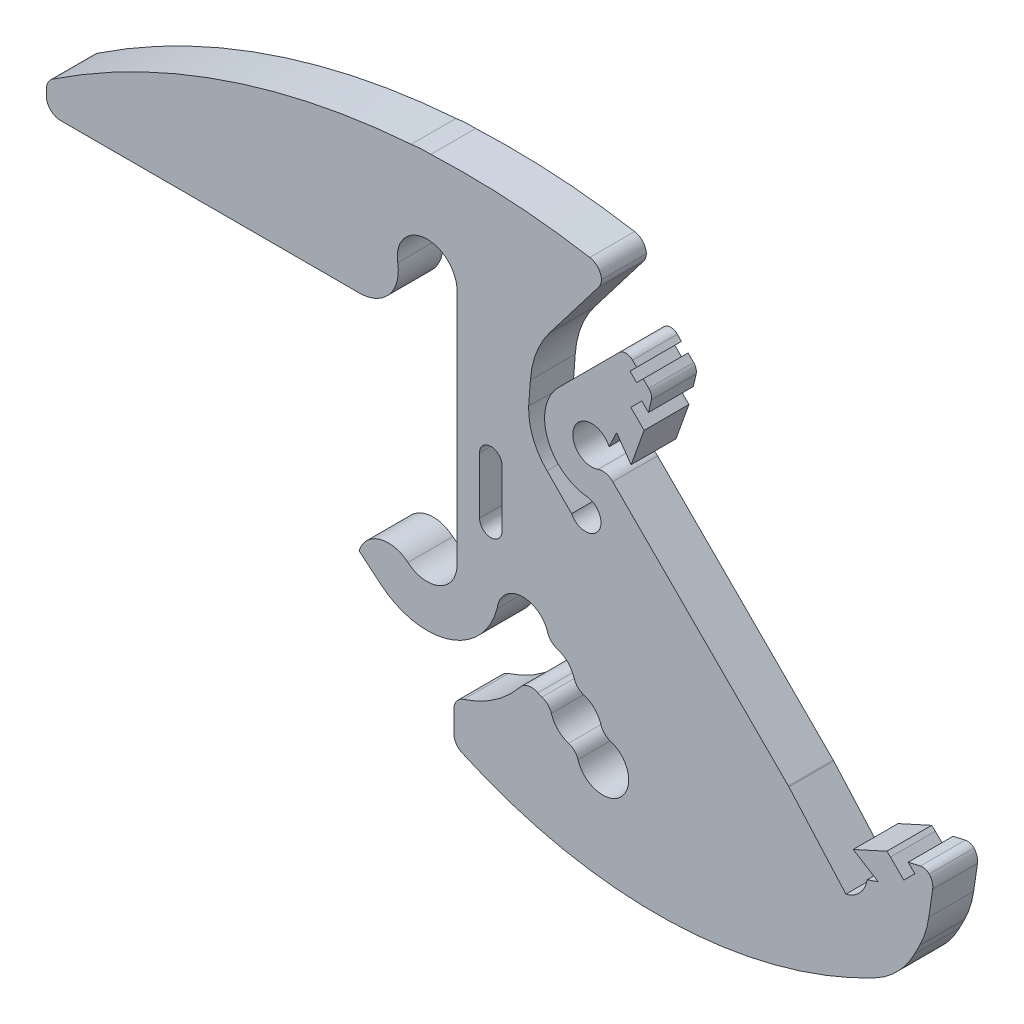
SolidWorks part; units mm, degrees
ref_plane "Front Plane" through (0, 0, 0) normal (0, 0, 1) x (1, 0, 0)
ref_plane "Top Plane" through (0, 0, 0) normal (0, 1, 0) x (1, 0, 0)
ref_plane "Right Plane" through (0, 0, 0) normal (1, 0, 0) x (0, 0, -1)
sketch "Main Geometry" plane through (0, 0, 0) normal (0, 0, 1) x (1, 0, 0)
  line L0 (0, -26.7735) -> (0, 29.7025) construction
  line L1 (-29.8398, 0) -> (33.7757, 0) construction
  line L2 (18, -21.6476) -> (18, 5) construction
  line L3 (18, 5) -> (48.2234, -25.2234) construction
  dimension "vertical offset" = 5
  dimension "horizontal offset" = 18
  dimension "device angle" = 45
sketch "Cart Clip Geometry" plane through (0, 0, 0) normal (0, 0, 1) x (1, 0, 0)
  line L0 (18, 9.2735) -> (18, -10.0482) construction
  line L1 (11.175, 4.575) -> (7.675, -8.575)
  line L2 (7.0852, 12.575) -> (-7.0852, 12.575) construction
  line L3 (-29.8398, 0) -> (33.7757, 0) construction
  line L4 (18, -21.6476) -> (18, 5) construction
  line L6 (-7.0852, 0) -> (7.0852, 0) construction
  line L7 (7.0852, -12.575) -> (-7.0852, -12.575) construction
  line L8 (0, 12.575) -> (-7.5717, 11.2399) construction
  line L9 (0, -12.575) -> (-5.2448, -18.8255) construction
  line L10 (3.175, 12.575) -> (3.175, -12.575)
  line L11 (-11.0052, 10.6345) -> (-10.7668, 9.2824)
  line L12 (-4.9334, -18.4544) -> (-7.2315, -16.526)
  line L13 (11.175, 4.575) -> (11.175, 12.575)
  line L14 (7.675, -12.575) -> (7.675, -8.575)
  arc A0 (-3.1268, 12.0237) -> (3.175, 12.575) centre (0, 12.575) cw
  arc A1 (-2.0409, -15.0072) -> (3.175, -12.575) centre (0, -12.575) ccw
  arc A2 (-11.0052, 10.6345) -> (11.175, 12.575) centre (0, 12.575) cw
  arc A3 (-4.9334, -18.4544) -> (7.675, -12.575) centre (0, -12.575) ccw
  arc A4 (-3.1268, 12.0237) -> (-10.7668, 9.2824) centre (-7.182, 11.3086) cw
  arc A5 (-2.0409, -15.0072) -> (-7.2315, -16.526) centre (-4.1299, -17.4968) ccw
  point P5 (0, 12.575)
  point P10 (0, 0)
  point P36 (18, -0.3874)
  dimension "D1" = 4
  dimension "rail radius" = 3.175
  dimension "bottom rail radius" = 3.175
  dimension "rail separation" = 12.575
  dimension "top clip grab angle" = 10
  dimension "bottom clip grab angle" = 50
  dimension "top clip thickness" = 8
  dimension "bottom clip thickness" = 4.5
  dimension "top clip end extension" = 1.3729
  dimension "bottom clip end extension" = 3
  dimension "top clip vertical extension" = 8
extrude "Cart Clip" add sketch "Cart Clip Geometry" against normal blind 4.7625
sketch "Device Clip Geometry" plane through (0, 0, 0) normal (0, 0, 1) x (1, 0, 0)
  line L0 (35.1404, -4.3761) -> (36.0403, -3.4762) construction
  line L1 (22.2452, 15.0879) -> (21.5381, 14.3808)
  line L2 (44.5165, -21.5165) -> (18, 5)
  line L3 (18, 5) -> (48.2234, -25.2234) construction
  line L4 (18, 5) -> (20.2451, 7.2451)
  line L5 (21.6593, 5.8309) -> (20.2451, 7.2451)
  line L6 (21.6593, 5.8309) -> (23.0381, 9.6846)
  line L7 (23.0381, 9.6846) -> (21.6239, 11.0988)
  line L8 (21.6239, 11.0988) -> (22.7977, 12.2726)
  line L9 (22.7977, 12.2726) -> (23.5048, 11.5655)
  line L10 (23.5048, 11.5655) -> (23.8045, 12.8639)
  line L11 (23.5372, 13.7959) -> (22.9502, 14.3828)
  line L12 (20.3936, 15.5253) -> (13.9341, 9.0659)
  line L13 (13.9341, 1.9948) -> (41.5113, -25.5824)
  line L14 (53.3124, -15.9793) -> (53.8993, -16.5663)
  line L15 (51.082, -16.0117) -> (52.3804, -15.712)
  line L16 (51.7891, -16.7188) -> (51.082, -16.0117)
  line L17 (50.6153, -17.8926) -> (51.7891, -16.7188)
  line L18 (49.2011, -16.4784) -> (50.6153, -17.8926)
  line L19 (45.3474, -17.8572) -> (49.2011, -16.4784)
  line L20 (45.3474, -17.8572) -> (46.7616, -19.2714)
  line L21 (44.5165, -21.5165) -> (46.7616, -19.2714)
  line L22 (55.0418, -19.1229) -> (48.5824, -25.5824)
  line L23 (21.5381, 14.3808) -> (22.2431, 13.6757)
  line L25 (22.2431, 13.6757) -> (22.9502, 14.3828)
  line L26 (22.2452, 15.0879) -> (21.8078, 15.5253)
  line L27 (53.1922, -17.2734) -> (53.8993, -16.5663)
  line L28 (53.8973, -17.9784) -> (53.1922, -17.2734)
  line L29 (54.6044, -17.2713) -> (53.8973, -17.9784)
  line L30 (54.6044, -17.2713) -> (55.0418, -17.7087)
  arc A0 (23.8045, 12.8639) -> (23.5372, 13.7959) centre (22.8301, 13.0888) ccw
  arc A1 (21.8078, 15.5253) -> (20.3936, 15.5253) centre (21.1007, 14.8182) ccw
  arc A2 (53.3124, -15.9793) -> (52.3804, -15.712) centre (52.6053, -16.6864) ccw
  arc A3 (55.0418, -17.7087) -> (55.0418, -19.1229) centre (54.3347, -18.4158) cw
  arc A4 (48.5824, -25.5824) -> (41.5113, -25.5824) centre (45.0468, -22.0468) cw
  arc A5 (13.9341, 9.0659) -> (13.9341, 1.9948) centre (17.4697, 5.5303) ccw
  point P3 (35.5903, -3.9262)
  point P17 (31.2583, -8.2583)
  point P28 (27.7227, -11.7938)
  point P30 (23.9291, 13.404)
  point P33 (21.1007, 16.2324)
  point P36 (52.9205, -15.5874)
  point P39 (55.7489, -18.4158)
  point P42 (45.0468, -29.1179)
  point P45 (10.3986, 5.5303)
  dimension "D2" = 1
  dimension "D3" = 1
  dimension "D5" = 5
  dimension "D1" = 4
  dimension "plate thickness" = 3.175
  dimension "board mating width" = 20.5
  dimension "board catch step" = 1
  dimension "plate to board offset" = 3.7
  dimension "board thickness" = 1.66
  dimension "above board offset" = 1.6
  dimension "overall width" = 24.5
  dimension "base thickness" = 5
  dimension "plate width" = 18.75
  dimension "D4" = 16.75
  dimension "board holding step" = 18.5
  dimension "D6" = 1.6186
  dimension "D7" = 0.9971
extrude "Device Clip" add sketch "Device Clip Geometry" against normal blind 4.7625
sketch "Device Clip Flex Relief Geometry" plane through (0, 0, 0) normal (0, 0, 1) x (1, 0, 0)
  line L0 (35.5903, -3.9262) -> (36.0403, -3.4762) construction
  circle A0 centre (17.4697, 5.5303) radius 2
  dimension "D1" = 4
sketch "Joint Geometry" plane through (0, 0, 0) normal (0, 0, 1) x (1, 0, 0)
  line L0 (7.675, -8.575) -> (41.5113, -25.5824)
  line L1 (41.5113, -25.5824) -> (13.9341, 1.9948)
  line L2 (13.9341, 1.9948) -> (11.175, 4.575)
  line L3 (11.175, 4.575) -> (7.675, -8.575)
extrude "Joint" add sketch "Joint Geometry" against normal blind 4.7625
fillet "joint fillets" radius 1 4 edges at (7.675, -8.575, -2.3813) (41.5113, -25.5824, -2.3813) (13.9341, 1.9948, -2.3813) (11.175, 4.575, -2.3813)
extrude "Device Clip Flex Relief" cut sketch "Device Clip Flex Relief Geometry" against normal through all
sketch "mark2" plane through (0, 0, 0) normal (0, 0, 1) x (1, 0, 0)
  circle A1 centre (3.175, 3.3755) radius 0.75
sketch "mark3" plane through (0, 0, 0) normal (0, 0, 1) x (1, 0, 0)
  circle A2 centre (3.175, 1.3755) radius 0.75
sketch "mark4" plane through (0, 0, 0) normal (0, 0, 1) x (1, 0, 0)
  circle A3 centre (3.175, -0.6245) radius 0.75
sketch "mark5" plane through (0, 0, 0) normal (0, 0, 1) x (1, 0, 0)
  circle A4 centre (3.175, -2.6245) radius 0.75
sketch "mark6" plane through (0, 0, 0) normal (0, 0, 1) x (1, 0, 0)
  circle A5 centre (3.175, -4.6245) radius 0.75
sketch "mark7" plane through (0, 0, 0) normal (0, 0, 1) x (1, 0, 0)
  circle A6 centre (3.175, -6.6245) radius 0.75
sketch "mark8" plane through (0, 0, 0) normal (0, 0, 1) x (1, 0, 0)
  circle A7 centre (3.175, -8.6245) radius 0.75
extrude "marker1" [suppressed] cut sketch "mark2" against normal blind 25
extrude "marker2" [suppressed] cut sketch "mark3" against normal blind 25
extrude "marker3" [suppressed] cut sketch "mark4" against normal blind 25
extrude "marker4" [suppressed] cut sketch "mark5" against normal blind 25
extrude "marker5" [suppressed] cut sketch "mark6" against normal blind 25
extrude "marker6" [suppressed] cut sketch "mark7" against normal blind 25
extrude "marker7" [suppressed] cut sketch "mark8" against normal blind 25
sketch "Sketch5" plane through (0, 0, 0) normal (0, 0, 1) x (1, 0, 0)
  line L0 (44.4701, -22.2536) -> (38.3891, -15.3891)
  line L1 (44.5165, -21.5165) -> (18.8839, 4.1161) construction
  line L2 (46.7616, -19.2714) -> (38.3891, -15.3891)
  line L3 (46.7616, -19.2714) -> (44.5165, -21.5165) construction
  arc A0 (46.7616, -19.2714) -> (44.4701, -22.2536) centre (43.7623, -19.3383) cw
extrude "SNAP IN RELIEF" cut sketch "Sketch5" against normal blind 6.35
sketch "BOTTOM BEEFUP SKETCH" plane through (0, 0, 0) normal (0, 0, 1) x (1, 0, 0)
  line L0 (10.677, -13.8895) -> (7.5264, -14.0782)
  line L1 (10.675, -9.2825) -> (44.2787, -25.4887)
  line L2 (44.2787, -25.4887) -> (53.8993, -16.5663)
  line L3 (53.8993, -16.5663) -> (55.0418, -17.7087)
  line L4 (50.3984, -26.8103) -> (55.3333, -21.8754)
  line L5 (7.5264, -14.0782) -> (7.2086, -8.7723)
  line L6 (7.2086, -8.7723) -> (10.675, -9.2825)
  line L7 (11.894, -16.9554) -> (10.677, -13.8895)
  line L8 (2.8283, -24.9304) -> (2.8283, -29.2389)
  arc A0 (55.0418, -17.7087) -> (55.3333, -21.8754) centre (52.7908, -19.9597) cw
  arc A1 (11.894, -16.9554) -> (2.8283, -24.9304) centre (0, -12.575) cw
  arc A2 (50.3984, -26.8103) -> (2.8283, -29.2389) centre (24.3794, 15.7331) cw
  arc A3 (-4.9334, -18.4544) -> (7.675, -12.575) centre (0, -12.575) ccw construction
  dimension "D1" = 5
extrude "BOTTOM BEEFUP" add sketch "BOTTOM BEEFUP SKETCH" against normal blind 4.7625
sketch "CABLE HOLE" plane through (0, 0, 0) normal (0, 0, 1) x (1, 0, 0)
  circle A0 centre (10.1626, -14.8178) radius 2.75
  dimension "D1" = 5.5
extrude "CABLE HOLE CUT" cut sketch "CABLE HOLE" against normal blind 6.35
sketch "BOX SLIDE BEEF" plane through (0, 0, 0) normal (0, 0, 1) x (1, 0, 0)
  line L0 (-7.182, 7.1908) -> (-40.4406, 7.1908)
  line L1 (-40.4406, 7.1908) -> (-40.4406, 10.131)
  line L2 (-40.4406, 10.131) -> (-4.1553, 22.9487)
  line L3 (-4.1553, 22.9487) -> (-7.182, 7.1908)
  arc A0 (-10.7668, 9.2824) -> (-3.1268, 12.0237) centre (-7.182, 11.3086) ccw construction
  arc A1 (11.175, 12.575) -> (-11.0052, 10.6345) centre (0, 12.575) ccw construction
extrude "SHELF TAIL" add sketch "BOX SLIDE BEEF" against normal blind 4.7625
sketch "BEHIND TOP CLIP BEEF SKETCH" plane through (0, 0, 0) normal (0, 0, 1) x (1, 0, 0)
  line L0 (18.5184, 20.8412) -> (11.175, 11.2548)
  line L1 (18.5184, 20.8412) -> (18.5184, 22.4809)
  line L2 (18.5184, 22.4809) -> (0.5901, 23.7344)
  line L3 (0.5901, 23.7344) -> (11.175, 11.2548)
  line L4 (11.175, 5.009) -> (11.175, 12.575) construction
  arc A0 (11.175, 12.575) -> (-4.1553, 22.9487) centre (0, 12.575) ccw construction
extrude "FRONT TAB BEEF" add sketch "BEHIND TOP CLIP BEEF SKETCH" against normal blind 4.7625
sketch "TOP CURVE" plane through (0, 0, 0) normal (0, 0, 1) x (1, 0, 0)
  line L0 (-40.4406, 10.131) -> (-38.7511, 8.7519)
  line L1 (-38.7511, 8.7519) -> (0, 16.8685)
  line L2 (0, 16.8685) -> (13.1756, 16.8685)
  line L3 (13.1756, 16.8685) -> (18.5184, 22.4809)
  arc A0 (-40.4406, 10.131) -> (18.5184, 22.4809) centre (4.0052, -55.1441) cw
extrude "TOP CURVE EXTRUSION" add sketch "TOP CURVE" against normal blind 4.7625
pattern_linear "LPattern1" count 4 spacing 4 along (0.7071, -0.7071, 0) of "CABLE HOLE CUT"
sketch "Sketch13" plane through (0, 0, 0) normal (0, 0, 1) x (1, 0, 0)
  line L0 (49.2011, -16.4784) -> (48.8113, -16.1381)
  line L1 (45.3474, -17.8572) -> (45.2375, -17.7613)
  line L2 (45.2375, -17.7613) -> (48.8113, -16.1381)
  line L3 (45.3474, -17.8572) -> (49.2011, -16.4784)
extrude "POSCON BOTTOM SNAPBEEF" add sketch "Sketch13" against normal blind 4.7625
sketch "Sketch14" plane through (0, 0, 0) normal (0, 0, 1) x (1, 0, 0)
  line L3 (12.7141, 0.8179) -> (15.3366, -1.8287)
  line L5 (12.471, 5.6443) -> (11.175, 11.2548)
  line L6 (11.175, 11.2548) -> (10.7789, 5.768)
  arc A0 (13.9181, 2.0109) -> (16.9732, 0.555) centre (17.4697, 5.5303) ccw
  arc A1 (12.471, 5.6443) -> (13.9181, 2.0109) centre (17.4697, 5.5303) ccw
  arc A2 (16.9732, 0.555) -> (15.3366, -1.8287) centre (16.8094, -1.0861) cw
  arc A3 (10.7789, 5.768) -> (12.7141, 0.8179) centre (17.4697, 5.5303) ccw
extrude "POSCON TOP CLIP FLEX RELIEF" cut sketch "Sketch14" against normal blind 6.35
sketch "Sketch15" plane through (0, 0, 0) normal (0, 0, 1) x (1, 0, 0)
  line L0 (6.7591, -1.122) -> (6.7591, -7.122) construction
  line L1 (7.9591, -1.122) -> (7.9591, -7.122)
  line L2 (5.5591, -1.122) -> (5.5591, -7.122)
  arc A0 (7.9591, -1.122) -> (5.5591, -1.122) centre (6.7591, -1.122) ccw
  arc A1 (5.5591, -7.122) -> (7.9591, -7.122) centre (6.7591, -7.122) ccw
  point P2 (6.7591, -4.122)
  dimension "D2" = 1.2
  dimension "D1" = 6
extrude "ZIP TIE SLOT" cut sketch "Sketch15" against normal blind 6.35
sketch "Sketch16" plane through (0, 0, 0) normal (0, 0, 1) x (1, 0, 0)
  line L0 (45.2375, -17.7613) -> (47.9015, -19.3975)
  line L1 (47.9015, -19.3975) -> (45.9622, -20.0708)
  line L2 (45.9622, -20.0708) -> (45.2375, -17.7613)
  line L3 (53.7888, -16.4558) -> (53.0401, -21.5945)
  line L4 (53.0401, -21.5945) -> (50.3984, -26.8103)
  line L5 (50.3984, -26.8103) -> (52.008, -28.2076)
  line L6 (52.008, -28.2076) -> (59.8175, -20.2354)
  line L7 (53.7888, -16.4558) -> (59.8175, -20.2354)
  line L8 (55.0418, -17.7087) -> (53.3124, -15.9793) construction
extrude "POSCON BOTTOM SNAP RELIEF" cut sketch "Sketch16" against normal blind 6.35
fillet "SMALL FILLET" radius 1.5 15 edges at (18.5184, 20.8412, -2.3813) (-40.4406, 7.1908, -2.3813) (12.9115, -14.8974, -2.3813) (15.7399, -17.7258, -2.3813) (18.5683, -20.5542, -2.3813) (13.0706, -20.3951, -2.3813) (15.899, -23.2235, -2.3813) (38.3891, -15.3891, -2.3813) (18.8839, 4.1161, -2.3813) (18.5184, 22.4809, -2.3813) (-40.4406, 10.131, -2.3813) (53.7888, -16.4558, -2.3813) (2.8283, -29.2389, -2.3813) (2.8283, -24.9304, -2.3813) (10.7667, -19.2633, -2.3813)
sketch "Sketch12" plane through (0, 0, 0) normal (0, 0, 1) x (1, 0, 0)
  line L0 (21.6593, 5.8309) -> (20.1191, 8.0153)
  line L1 (20.1191, 8.0153) -> (19.311, 6.311)
  line L2 (21.6593, 5.8309) -> (19.311, 6.311)
  line L3 (20.2451, 7.2451) -> (21.6593, 5.8309) construction
  arc A1 (19.311, 6.311) -> (18.1413, 3.6465) centre (17.4697, 5.5303) ccw construction
extrude "POSCON TOP SNAP RELIEF" cut sketch "Sketch12" against normal blind 6.35
sketch "poscon cross section slide in" plane through (0, 0, 0) normal (0, 0, 1) x (1, 0, 0)
  line L0 (21.0676, 7.5064) -> (44.3228, -21.9121)
  line L1 (44.3228, -21.9121) -> (46.6763, -20.0516)
  line L2 (46.6763, -20.0516) -> (23.4211, 9.3668)
  line L3 (23.4211, 9.3668) -> (21.0676, 7.5064)
  dimension "D1" = 37.5
  dimension "D2" = 3
fillet "LARGE FILLET" radius 10 3 edges at (50.3984, -26.8103, -2.3813) (53.0401, -21.5945, -2.3813) (11.175, 11.2548, -2.3813)
equation "\"thick\"= .1875in"
equation "\"D1@Cart Clip\"=\"thick\""
equation "\"D1@Device Clip\"=\"thick\""
equation "\"D1@Joint\"=\"thick\""
equation "\"D1@BOTTOM BEEFUP\"=\"thick\""
equation "\"D1@SHELF TAIL\"=\"thick\""
equation "\"D1@FRONT TAB BEEF\"=\"thick\""
equation "\"D1@TOP CURVE EXTRUSION\"=\"thick\""
equation "\"D1@POSCON BOTTOM SNAPBEEF\"=\"thick\""
